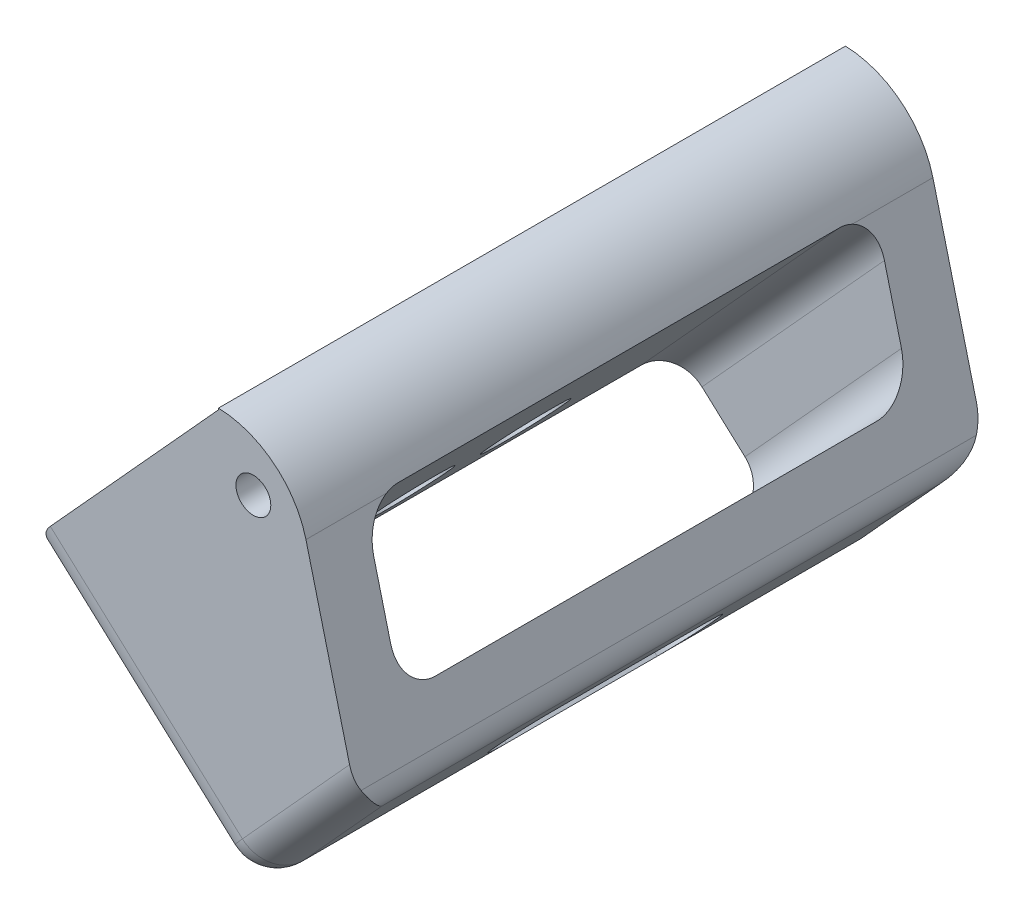
SolidWorks part; units mm, degrees
ref_plane "前视基准面" through (0, 0, 0) normal (0, 0, 1) x (1, 0, 0)
ref_plane "上视基准面" through (0, 0, 0) normal (0, 1, 0) x (1, 0, 0)
ref_plane "右视基准面" through (0, 0, 0) normal (1, 0, 0) x (0, 0, -1)
other "Configuration Table"
sketch "草图1" plane through (0, 0, 0) normal (0, 0, 1) x (1, 0, 0)
  line L1 (-3.0065, 5) -> (3.0065, 5)
  line L2 (-3.0065, 5) -> (-3.0065, -5)
  line L3 (-3.0065, -5) -> (3.0065, -5)
  line L4 (3.0065, 5) -> (3.0065, -5)
  line L5 (-3.0065, 5) -> (3.0065, -5) construction
  line L6 (-3.0065, -5) -> (3.0065, 5) construction
  circle A0 centre (0, 0) radius 1.5
  dimension "D1" = 3
  dimension "D2" = 10
extrude "凸台-拉伸1" add sketch "草图1" along normal blind 54
sketch "草图2" plane through (0, 0, 54) normal (0, 0, 1) x (1, 0, 0)
  line L0 (-5.3336, 2.3094) -> (-11.3877, -4.3501) construction
  line L1 (-5.3336, 2.3094) -> (-11.3877, -4.3501)
  line L2 (-5.3336, 2.3094) -> (-3.0065, 4.8692)
  line L3 (-3.0065, 5) -> (-3.0065, -5) construction
  line L4 (3.0065, 5) -> (9.1647, -19.4455)
  line L5 (9.1647, -19.4455) -> (-0.7403, -30.341)
  line L6 (-0.7403, -30.341) -> (-19.5065, -13.2808)
  line L7 (-19.5065, -13.2808) -> (-11.3877, -4.3501)
  line L8 (3.0065, -5) -> (3.0065, 5)
  line L9 (3.0065, 5) -> (-3.0065, 5)
  line L10 (-3.0065, 5) -> (-3.0065, -5)
  line L11 (-3.0065, -5) -> (3.0065, -5)
  line L12 (3.0065, -5) -> (3.0065, 5)
  line L13 (3.0065, 5) -> (-3.0065, 5)
  line L14 (-3.0065, 5) -> (-3.0065, -5)
  line L15 (-3.0065, -5) -> (3.0065, -5)
  point P12 (9.1647, -19.4455)
  line M8 (3.0065, -5) -> (3.0065, 5)
  line M10 (-3.0065, 5) -> (-3.0065, -5)
  line M11 (-3.0065, -5) -> (3.0065, -5)
  dimension "D1" = 0
extrude "凸台-拉伸2" add sketch "草图2" against normal blind 54 contours L7 L6 L5 L4 L2 L1 M8 M11 M10 region at (-3.6106, -13.7667, 54)
sketch "草图3" plane through (-15.4369, -16.9805, 0) normal (-0.6727, -0.7399, 0) x (0.7399, -0.6727, 0)
  line L0 (14.8618, 49) -> (3.8613, 49)
  line L1 (3.8613, 49) -> (3.8613, 5)
  line L2 (3.8613, 5) -> (14.8618, 5)
  line L3 (14.8618, 5) -> (14.8618, 49)
  line L4 (19.8618, 54) -> (-1.1387, 54)
  line L5 (19.8618, 0) -> (19.8618, 54)
  line L6 (-1.1387, 0) -> (19.8618, 0)
  line L7 (-1.1387, 54) -> (-1.1387, 0)
  line L8 (19.8618, 54) -> (-1.1387, 54)
  line L9 (19.8618, 0) -> (19.8618, 54)
  line L10 (-1.1387, 0) -> (19.8618, 0)
  line L11 (-1.1387, 54) -> (-1.1387, 0)
  dimension "D1" = 0
  dimension "D2" = 5
extrude "切除-拉伸1" cut sketch "草图3" against normal blind 54 contours L2 L3 L0 L1 region at (-8.5099, -23.2778, 27)
fillet "圆角1" radius 3 11 edges at (-4.0535, -10.1991, 49) (1.6293, -20.3015, 5) (-4.0535, -10.1991, 5) (1.6293, -20.3015, 49) (-10.1234, -21.8109, 0) (-10.1234, -21.8109, 54) (-0.7403, -30.341, 27) (9.1647, -19.4455, 27) (-19.5065, -13.2808, 27) (4.2122, -24.8933, 0) (4.2122, -24.8933, 54)
sketch "草图4" plane through (-4.0697, 3.6997, 0) normal (-0.7399, 0.6727, 0) x (0, 0, 1)
  line L0 (0, 1.5805) -> (54, 1.5805) construction
  line L1 (0, 1.5805) -> (54, 1.5805)
  line L2 (27, 1.5805) -> (27, -19.9485) construction
  line L3 (0, -19.9485) -> (54, -19.9485) construction
  circle A0 centre (22, -16.9485) radius 1.5
  circle A1 centre (32, -16.9485) radius 1.5
  point P10 (22.4021, -1.3616)
  dimension "D1" = 3
  dimension "D2" = 3
  dimension "D3" = 5
extrude "切除-拉伸2" cut sketch "草图4" against normal through all contours A0 | A1 region at (-15.4705, -8.8412, 22) region at (-15.4705, -8.8412, 32)
sketch "草图5" plane through (14.6965, -13.3605, 0) normal (0.7399, -0.6727, 0) x (0, 0, -1)
  line L0 (-33.5, -16.9485) -> (-30.5, -16.9485) construction
  line L1 (-33.5, -13.9485) -> (-30.5, -13.9485)
  line L2 (-33.5, -19.9485) -> (-30.5, -19.9485)
  line L3 (-23.5, -16.9485) -> (-20.5, -16.9485) construction
  line L4 (-23.5, -13.9485) -> (-20.5, -13.9485)
  line L5 (-23.5, -19.9485) -> (-20.5, -19.9485)
  line L6 (-30.5, -13.9485) -> (-23.5, -13.9485)
  line L7 (-23.5, -19.9485) -> (-30.5, -19.9485)
  circle A0 centre (-22, -16.9485) radius 1.5 construction
  circle A1 centre (-32, -16.9485) radius 1.5 construction
  circle A2 centre (-22, -16.9485) radius 1.5
  circle A3 centre (-32, -16.9485) radius 1.5
  arc A4 (-33.5, -13.9485) -> (-33.5, -19.9485) centre (-33.5, -16.9485) ccw
  arc A5 (-30.5, -19.9485) -> (-30.5, -13.9485) centre (-30.5, -16.9485) ccw
  arc A6 (-23.5, -13.9485) -> (-23.5, -19.9485) centre (-23.5, -16.9485) ccw
  arc A7 (-20.5, -19.9485) -> (-20.5, -13.9485) centre (-20.5, -16.9485) ccw
  point P8 (-32, -16.9485)
  point P15 (-22, -16.9485)
  circle M7 centre (-32, -16.9485) radius 1.5
  circle M8 centre (-22, -16.9485) radius 1.5
  dimension "D2" = 3
  dimension "D3" = 3
  dimension "D1" = 3
extrude "切除-拉伸3" cut sketch "草图5" against normal blind 8 contours L2 A5 L1 A4 M7 | A6 L6 A5 L7 | L5 A7 L4 A6 M8 region at (5.241, -23.7616, 32) region at (3.2957, -25.9014, 27) region at (5.241, -23.7616, 22)
sketch "草图6" plane through (2.8571, -2.5974, 0) normal (0.7399, -0.6727, 0) x (0, 0, -1)
  circle A0 centre (-22, -16.9485) radius 1.5 construction
  circle A1 centre (-32, -16.9485) radius 1.5 construction
  circle A2 centre (-22, -16.9485) radius 1.5
  circle A3 centre (-32, -16.9485) radius 1.5
  circle A4 centre (-32, -16.9485) radius 3.25
  circle A5 centre (-22, -16.9485) radius 3.25
  dimension "D1" = 6.5
extrude "切除-拉伸4" cut sketch "草图6" against normal blind 2.5
fillet "圆角2" radius 8 1 edges at (3.0065, 5, 27)
